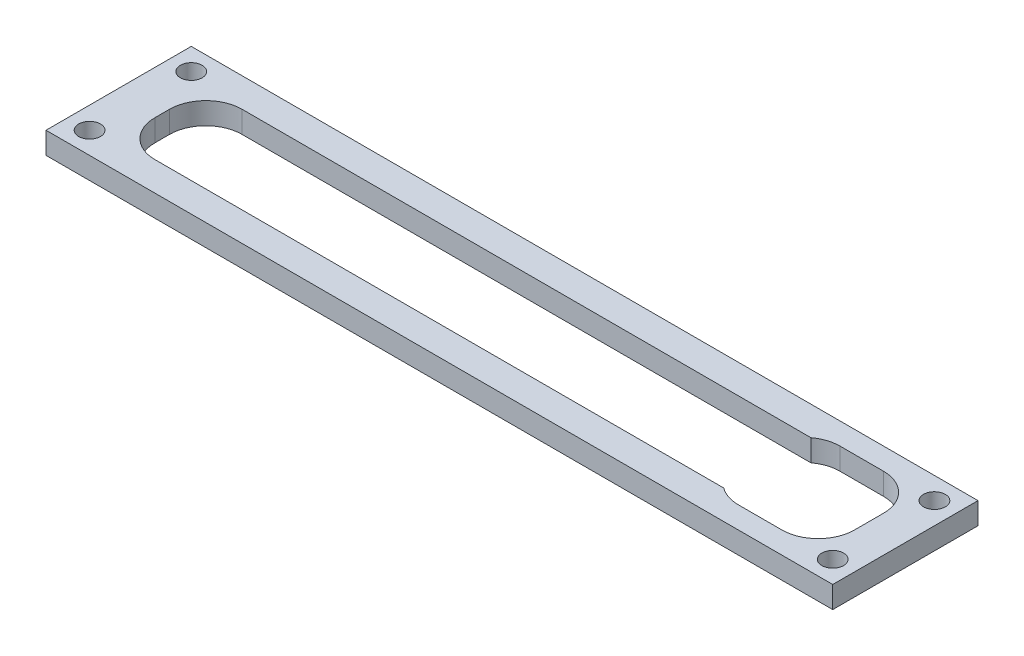
SolidWorks part; units mm, degrees
ref_plane "Front Plane" through (0, 0, 0) normal (0, 0, 1) x (1, 0, 0)
ref_plane "Top Plane" through (0, 0, 0) normal (0, 1, 0) x (1, 0, 0)
ref_plane "Right Plane" through (0, 0, 0) normal (1, 0, 0) x (0, 0, -1)
sketch "Sketch1" plane through (0, 0, 0) normal (0, 1, 0) x (1, 0, 0)
  line L0 (54.1604, 20) -> (54.1604, 0) construction
  line L1 (0, 0) -> (108.3209, 0)
  line L2 (0, 0) -> (0, 20)
  line L3 (0, 20) -> (108.3209, 20)
  line L4 (108.3209, 0) -> (108.3209, 20)
  line L5 (0, 10) -> (108.3209, 10) construction
  line L6 (54.1604, 16) -> (54.1604, 4) construction
  line L7 (6, 16) -> (102.3209, 16)
  line L8 (6, 16) -> (6, 4)
  line L9 (6, 4) -> (102.3209, 4)
  line L10 (102.3209, 16) -> (102.3209, 4)
  line L11 (6, 10) -> (102.3209, 10) construction
  circle A0 centre (3, 17) radius 1.5
  circle A1 centre (3, 3) radius 1.5
  circle A2 centre (105.3209, 3) radius 1.5
  circle A3 centre (105.3209, 17) radius 1.5
  point P17 (54.1604, 10)
  point P18 (54.1604, 10)
  dimension "D7" = 3
  dimension "D1" = 108.3209
  dimension "D2" = 20
  dimension "D3" = 96.3209
  dimension "D4" = 12
  dimension "D5" = 3
  dimension "D6" = 3
extrude "Boss-Extrude1" add sketch "Sketch1" along normal blind 3
sketch "Sketch2" plane through (0, 3, 0) normal (0, 1, 0) x (1, 0, 0)
  line L0 (92, 10) -> (-49908, 10) construction
  line L1 (102.3209, 4) -> (102.3209, 16) construction
  line L2 (89.3209, 17) -> (89.3209, 16)
  line L5 (102.3209, 16) -> (6, 16) construction
  line L6 (96.3209, 17) -> (96.3209, 3) construction
  line L7 (89.3209, 17) -> (103.3209, 17)
  line L9 (89.3209, 3) -> (103.3209, 3)
  line L10 (103.3209, 17) -> (103.3209, 3)
  line L12 (89.3209, 16) -> (102.3209, 16)
  line L13 (102.3209, 16) -> (102.3209, 4)
  line L14 (102.3209, 4) -> (89.3209, 4)
  line L15 (6, 4) -> (102.3209, 4) construction
  line L16 (89.3209, 4) -> (89.3209, 3)
  point P4 (102.3209, 10)
  point P23 (96.3209, 10)
  dimension "D1" = 1
  dimension "D2" = 14
  dimension "D3" = 14
extrude "Cut-Extrude1" cut sketch "Sketch2" against normal through all
fillet "Fillet1" radius 5 6 edges at (103.3209, 1.5, -17) (103.3209, 1.5, -3) (89.3209, 1.5, -17) (89.3209, 1.5, -3) (6, 1.5, -4) (6, 1.5, -16)
equation "\"TrackLength\"= ( ( \"n\" * 28 ) ) / cos ( \"MountAngle\" ) - ( 2 * \"x\" )"
equation "\"D1@Sketch1\"=\"TrackLength\""
equation "\"TrackWidth\"= \"MarbleTrackWidth\" + ( 2 * 4 )"
equation "\"D2@Sketch1\"=\"TrackWidth\""
equation "\"MarbleTrackWidth\"= \"MarbleWidth\" - 1"
equation "\"MarbleTrackLength\"= \"TrackLength\" - ( 2 * 6 )"
equation "\"D3@Sketch1\"=\"MarbleTrackLength\""
equation "\"D4@Sketch1\"=\"MarbleTrackWidth\""
equation "\"MarbleWidth\"= 13"
equation "\"n\"= 4"
equation "\"MountAngle\"= 5"
equation "\"x\"= 14 / cos ( \"MountAngle\" ) - 12"
